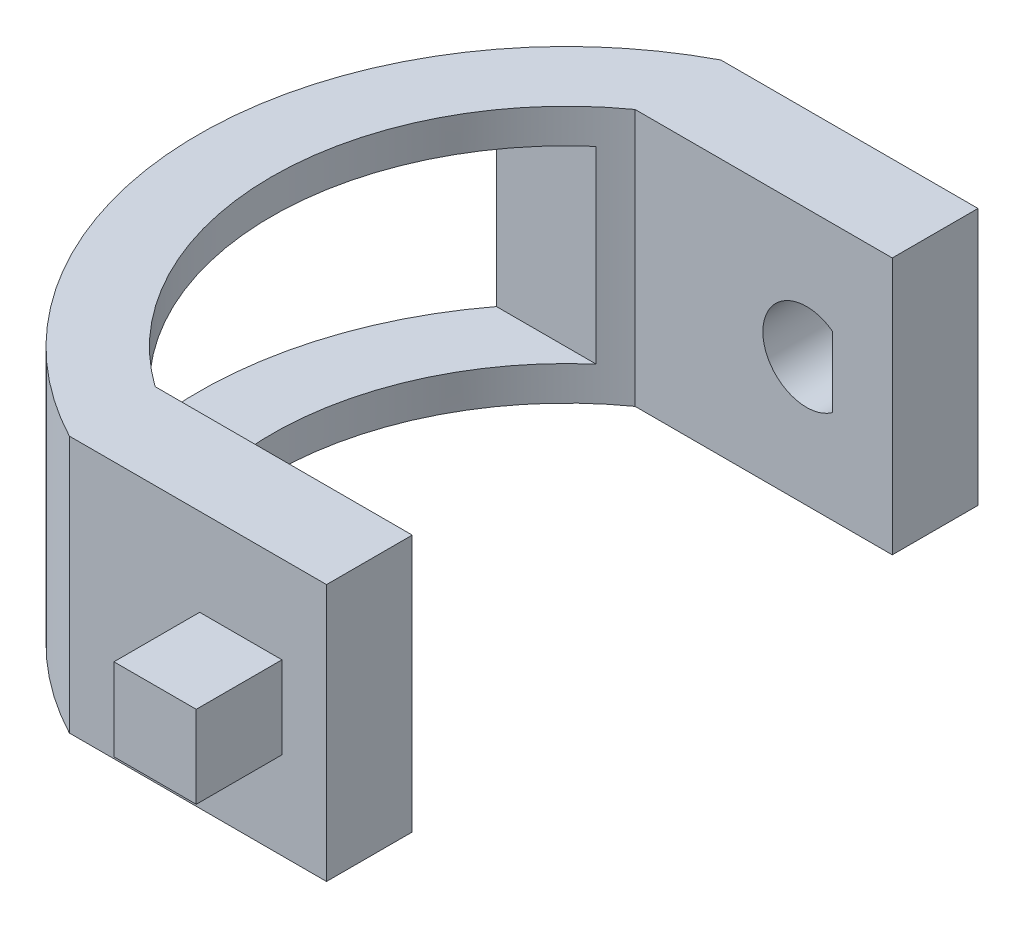
SolidWorks part; units mm, degrees
note: The reader was unsure of these and kept them because the rebuilt part matched: shared geometry of "Skizze7<4>", "Skizze7<3>".
ref_plane "Ebene vorne" through (0, 0, 0) normal (0, 0, 1) x (1, 0, 0)
ref_plane "Ebene oben" through (0, 0, 0) normal (0, 1, 0) x (1, 0, 0)
ref_plane "Ebene rechts" through (0, 0, 0) normal (1, 0, 0) x (0, 0, -1)
sketch "Skizze7"
  line L1 (0, 0) -> (4.8, 0)
  line L2 (0, 0) -> (0, -4.8)
  line L3 (0, -4.8) -> (4.8, -4.8)
  line L4 (4.8, 0) -> (4.8, -4.8)
  line L5 (-7.6, -9.9) -> (7.4, -9.9)
  line L6 (-7.6, -9.9) -> (-7.6, 5.1)
  line L7 (-7.6, 5.1) -> (7.4, 5.1)
  line L8 (7.4, -9.9) -> (7.4, 5.1)
  dimension "D1" = 4.8
  dimension "D2" = 4.8
  dimension "D3" = 15
  dimension "D4" = 15
  dimension "D5" = 2.6
  dimension "D6" = 5.1
sketch "Skizze7<4>" plane through (0, 0, 0) normal (0, 0, 1) x (1, 0, 0) same geometry as "Skizze7"
extrude "Aufsatz-Linear austragen3" add sketch "Skizze7" along normal blind 5
extrude "Aufsatz-Linear austragen4" add sketch "Skizze7<3>" against normal blind 5 contours L4 L1 L2 L3 | L5 L8 L7 L6 L1 L4 L3 L2
sketch "Skizze7<3>" same geometry as "Skizze7"
extrude "Aufsatz-Linear austragen5" add sketch "Skizze7<4>" along normal blind 5 from offset 38 separate body contours L4 L1 L2 L3 offset against normal yes
sketch "Skizze9" plane through (0, 5.1, 0) normal (0, 1, 0) x (1, 0, 0)
  line L0 (7.4, 5) -> (7.4, 0) construction
  line L1 (-7.6, 0) -> (-7.6, 5)
  line L2 (-7.6, 33) -> (-7.6, 38)
  arc A0 (-7.6, 5) -> (-7.6, 33) centre (2.4, 19) cw
  arc A1 (-7.6, 0) -> (-7.6, 38) centre (2.4, 19) cw
  dimension "D1" = 5
  dimension "D2" = 5
extrude "Aufsatz-Linear austragen6" add sketch "Skizze9" against normal blind 15 contours A1 L2 A0 L1
sketch "Skizze11" plane through (0, 0, -38) normal (0, 0, -1) x (-1, 0, 0)
  line L0 (7.6, -9.9) -> (-7.4, -9.9) construction
  line L1 (-7.4, -9.9) -> (-7.4, 5.1) construction
  line L2 (-3.9, -4.4622) -> (-3.9, -0.3378)
  circle A0 centre (-2.4, -2.4) radius 2.55
  dimension "D3" = 5.1
  dimension "D1" = 7.5
  dimension "D2" = 5
  dimension "D4" = 1.5
extrude "Schnitt-Linear austragen6" cut sketch "Skizze11" against normal up to next contours L2 A0
sketch "Skizze12" plane through (7.4, 0, 0) normal (1, 0, 0) x (0, 0, -1)
  line L0 (5, -9.9) -> (0, -9.9) construction
  line L1 (6, -7.9) -> (32, -7.9)
  line L2 (6, -7.9) -> (6, 3.1)
  line L3 (6, 3.1) -> (32, 3.1)
  line L4 (32, -7.9) -> (32, 3.1)
  line L5 (5, 5.1) -> (0, 5.1) construction
  line L6 (5, -9.9) -> (5, 5.1) construction
  line L7 (33, -9.9) -> (33, 5.1) construction
  dimension "D1" = 2
  dimension "D2" = 2
  dimension "D3" = 1
  dimension "D4" = 1
extrude "Schnitt-Linear austragen7" cut sketch "Skizze12" against normal up to next contours L1 L4 L3 L2
